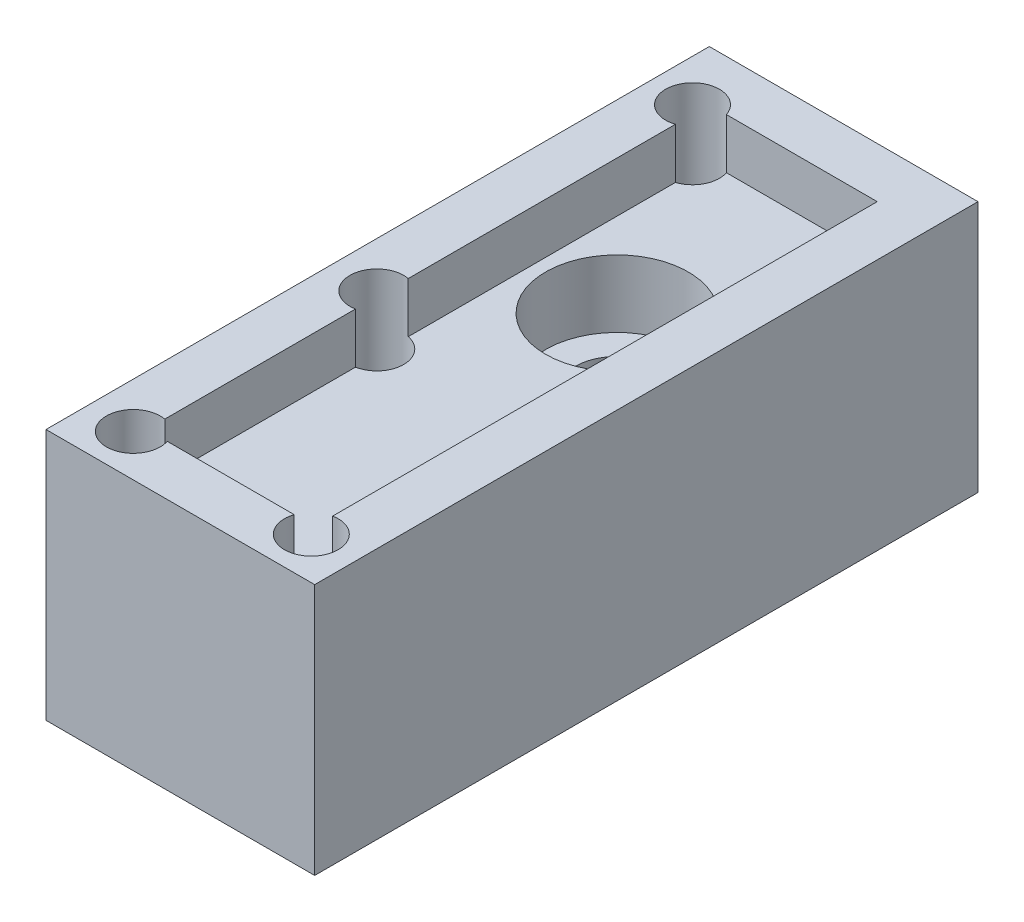
SolidWorks part; units mm, degrees
ref_plane "Front Plane" through (0, 0, 0) normal (0, 0, 1) x (1, 0, 0)
ref_plane "Top Plane" through (0, 0, 0) normal (0, 1, 0) x (1, 0, 0)
ref_plane "Right Plane" through (0, 0, 0) normal (1, 0, 0) x (0, 0, -1)
sketch "Sketch1" plane through (0, 0, 0) normal (0, 1, 0) x (1, 0, 0)
  line L1 (0, 0) -> (16, 0)
  line L2 (0, 0) -> (0, 39.5)
  line L3 (0, 39.5) -> (16, 39.5)
  line L4 (16, 0) -> (16, 39.5)
extrude "Boss-Extrude1" add sketch "Sketch1" along normal blind 15
sketch "Sketch2" plane through (0, 15, 0) normal (0, 1, 0) x (1, 0, 0)
  line L1 (3, 3) -> (13, 3)
  line L2 (3, 3) -> (3, 36.5)
  line L3 (3, 36.5) -> (13, 36.5)
  line L4 (13, 3) -> (13, 36.5)
extrude "Cut-Extrude1" cut sketch "Sketch2" against normal blind 3
sketch "Sketch3" plane through (0, 12, 0) normal (0, 1, 0) x (1, 0, 0)
  circle A0 centre (2.7, 2.5) radius 1.6
extrude "Cut-Extrude2" cut sketch "Sketch3" against normal through all and the other way through all
sketch "Sketch4" plane through (0, 15, 0) normal (0, 1, 0) x (1, 0, 0)
  circle A0 centre (13.3, 2.5) radius 1.6
  circle A1 centre (2.7, 17) radius 1.6
  circle A2 centre (2.5, 36) radius 1.6
extrude "Cut-Extrude3" cut sketch "Sketch4" against normal through all and the other way blind 3
sketch "Sketch5" plane through (0, 12, 0) normal (0, 1, 0) x (1, 0, 0)
  circle A0 centre (8, 26) radius 2.5
extrude "Cut-Extrude4" cut sketch "Sketch5" against normal blind 20
sketch "Sketch7" plane through (0, 12, 0) normal (0, 1, 0) x (1, 0, 0)
  circle A0 centre (8, 26) radius 4.25
extrude "Cut-Extrude5" cut sketch "Sketch7" against normal blind 4
